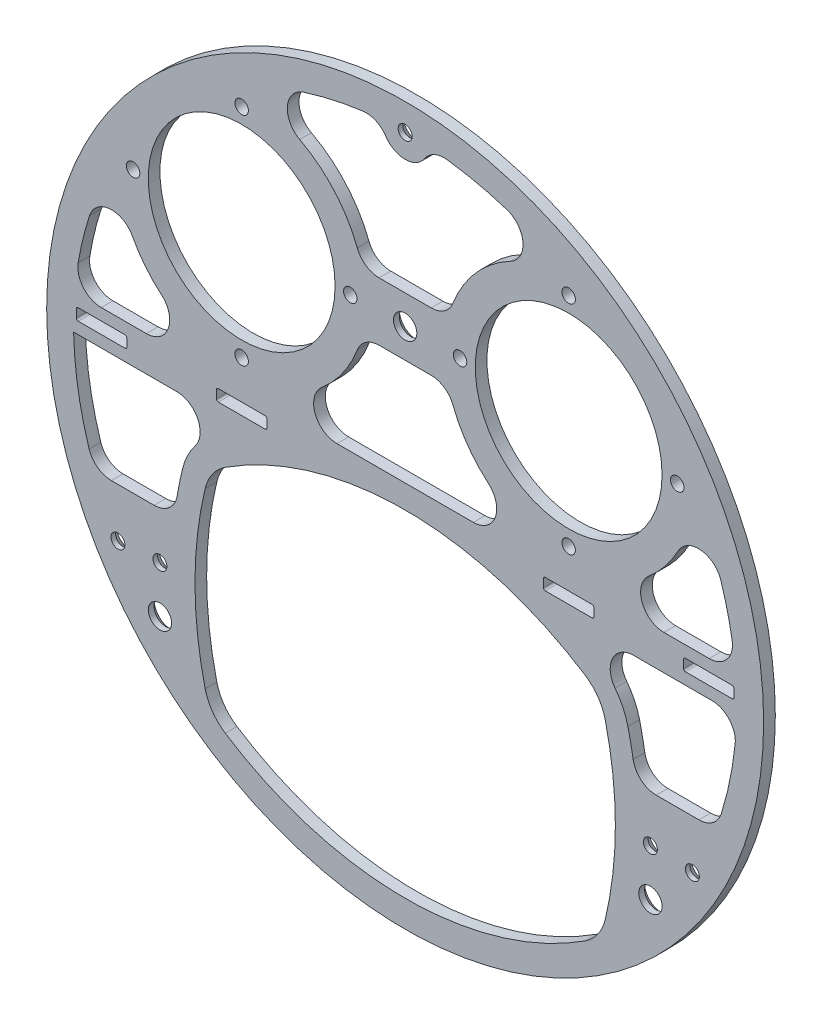
SolidWorks part; units mm, degrees
ref_plane "Front Plane" through (0, 0, 0) normal (0, 0, 1) x (1, 0, 0)
ref_plane "Top Plane" through (0, 0, 0) normal (0, 1, 0) x (1, 0, 0)
ref_plane "Right Plane" through (0, 0, 0) normal (1, 0, 0) x (0, 0, -1)
sketch "Sketch1" plane through (0, 0, 0) normal (0, 0, 1) x (1, 0, 0)
  circle A0 centre (0, 0) radius 97.4725
  circle A1 centre (0, 0) radius 90.17
  dimension "D1" = 194.945
  dimension "D2" = 180.34
extrude "Boss-Extrude1" add sketch "Sketch1" along normal blind 3.175
sketch "Sketch2" plane through (0, 0, 3.175) normal (0, 0, 1) x (1, 0, 0)
  arc A5 (-5.2915, 86.6596) -> (5.2915, 86.6596) centre (0, 90.17) ccw
  circle A6 centre (0, 0) radius 90.17 construction
  arc A8 (-5.2915, 86.6596) -> (-11.3847, 89.4484) centre (-10.5829, 83.1492) ccw
  arc A9 (5.2915, 86.6596) -> (11.3847, 89.4484) centre (10.5829, 83.1492) cw
  arc A10 (11.3847, 89.4484) -> (-11.3847, 89.4484) centre (0, 0) ccw
  dimension "D3" = 6.35
  dimension "D4" = 6.35
extrude "Boss-Extrude2" add sketch "Sketch2" against normal up to surface (3.175 mm away) up to face at (97.4725, 0, 0)
hole_wizard "CSK for #6 Flat Head Machine Screw2" positions "Sketch8" profile "Sketch7" countersink size "#6" standard "ANSI Inch" end condition through all
sketch "Sketch8" plane through (0, 0, 0) normal (0, 0, -1) x (-1, 0, 0)
  point P0 (0, 90.17)
sketch "Sketch7" plane through (0, 90.17, 0) normal (1, 0, 0) x (0, 1, 0)
  line L0 (0, 0) -> (0, 3.175)
  line L1 (0, 3.175) -> (1.8986, 3.175)
  line L2 (1.8986, 3.175) -> (1.8986, 1.892)
  line L3 (1.8986, 1.892) -> (3.5433, 0)
  line L5 (3.5433, 0) -> (0, 0)
  line L6 (-1.8986, 1.892) -> (-3.5433, 0) construction
  line L11 (0, -6.35) -> (0, 107.95) construction
  dimension "Thru Hole Dia." = 3.7973
  dimension "Thru Hole Depth" = 3.175
  dimension "Near C'Sink Dia." = 7.0866
  dimension "Near C'Sink Angle" = 82
pattern_circular "CirPattern2" count 3 over 360 about axis through (0, 0, 0) along (0, 0, 1) of "CSK for #6 Flat Head Machine Screw2", "Boss-Extrude2"
sketch "Sketch9" plane through (0, 0, 0) normal (0, 0, 1) x (1, 0, 0)
  line L0 (44.45, -44.45) -> (-44.45, -44.45) construction
  line L1 (0, 0) -> (0, 1.109) construction
  arc A0 (48.9116, -13.1485) -> (-48.9116, -13.1485) centre (0, -88.9) ccw
  arc A1 (-54.3759, -20.8703) -> (-54.3759, -68.0297) centre (44.45, -44.45) ccw
  arc A2 (-48.9116, -75.7515) -> (48.9116, -75.7515) centre (0, 0) ccw
  arc A3 (-48.9116, -75.7515) -> (-54.3759, -68.0297) centre (-42.0227, -65.0822) cw
  arc A4 (48.9116, -75.7515) -> (54.3759, -68.0297) centre (42.0227, -65.0822) ccw
  arc A5 (54.3759, -68.0297) -> (54.3759, -20.8703) centre (-44.45, -44.45) ccw
  arc A6 (48.9116, -13.1485) -> (54.3759, -20.8703) centre (42.0227, -23.8178) cw
  arc A7 (-48.9116, -13.1485) -> (-54.3759, -20.8703) centre (-42.0227, -23.8178) ccw
  arc A8 (-71.7723, -54.5836) -> (71.7723, -54.5836) centre (0, 0) ccw construction
  arc A9 (-60.5525, -19.3966) -> (-60.5525, -69.5034) centre (44.45, -44.45) ccw
  arc A10 (-52.3561, -81.0861) -> (-60.5525, -69.5034) centre (-42.0227, -65.0822) cw
  arc A11 (-52.3561, -81.0861) -> (52.3561, -81.0861) centre (0, 0) ccw
  arc A12 (52.3561, -81.0861) -> (60.5525, -69.5034) centre (42.0227, -65.0822) ccw
  arc A13 (60.5525, -69.5034) -> (60.5525, -19.3966) centre (-44.45, -44.45) ccw
  arc A14 (52.3561, -7.8139) -> (60.5525, -19.3966) centre (42.0227, -23.8178) cw
  arc A15 (52.3561, -7.8139) -> (-52.3561, -7.8139) centre (0, -88.9) ccw
  arc A16 (-52.3561, -7.8139) -> (-60.5525, -19.3966) centre (-42.0227, -23.8178) ccw
  dimension "D1" = 12.7
  dimension "D4" = 101.6
  dimension "D2" = 44.45
  dimension "D3" = 88.9
  dimension "D5" = 6.35
extrude "Boss-Extrude3" add sketch "Sketch9" along normal up to surface (3.175 mm away) up to face at (-79.9882, -45.085, 3.175)
fillet "Fillet1" radius 3.175 2 edges at (61.3011, -66.1271, 1.5875) (-61.3011, -66.1271, 1.5875)
sketch "Sketch10" plane through (0, 0, 0) normal (0, 0, -1) x (-1, 0, 0)
  line L0 (-84.3953, -31.75) -> (-62.7503, -31.75)
  line L1 (62.7503, -31.75) -> (84.3953, -31.75)
  arc A0 (-11.3847, 89.4484) -> (-83.1569, -34.8648) centre (0, 0) ccw construction
  arc A1 (-60.5525, -19.3966) -> (-62.8448, -56.3258) centre (44.45, -44.45) ccw construction
  arc A2 (62.8448, -56.3258) -> (60.5525, -19.3966) centre (-44.45, -44.45) ccw construction
  arc A3 (83.1569, -34.8648) -> (11.3847, 89.4484) centre (0, 0) ccw construction
  arc A4 (-83.1569, -34.8648) -> (-77.6952, -38.7473) centre (-77.3008, -32.4095) ccw construction
  arc A5 (-72.4037, -47.9124) -> (-77.6952, -38.7473) centre (-78.0895, -45.085) ccw construction
  arc A6 (-72.4037, -47.9124) -> (-71.7723, -54.5836) centre (-66.7179, -50.7397) ccw construction
  arc A7 (-71.7723, -54.5836) -> (-68.4093, -58.7435) centre (0, 0) ccw construction
  arc A8 (-68.4093, -58.7435) -> (-62.8448, -56.3258) centre (-66.0005, -56.6751) ccw construction
  arc A9 (62.8448, -56.3258) -> (68.4093, -58.7435) centre (66.0005, -56.6751) ccw construction
  arc A10 (68.4093, -58.7435) -> (71.7723, -54.5836) centre (0, 0) ccw construction
  arc A11 (71.7723, -54.5836) -> (72.4037, -47.9124) centre (66.7179, -50.7397) ccw construction
  arc A12 (77.6952, -38.7473) -> (72.4037, -47.9124) centre (78.0895, -45.085) ccw construction
  arc A13 (77.6952, -38.7473) -> (83.1569, -34.8648) centre (77.3008, -32.4095) ccw construction
  arc A14 (-84.3953, -31.75) -> (-83.1569, -34.8648) centre (0, 0) ccw
  arc A15 (-83.1569, -34.8648) -> (-77.6952, -38.7473) centre (-77.3008, -32.4095) ccw
  arc A16 (-72.4037, -47.9124) -> (-77.6952, -38.7473) centre (-78.0895, -45.085) ccw
  arc A17 (-72.4037, -47.9124) -> (-71.7723, -54.5836) centre (-66.7179, -50.7397) ccw
  arc A18 (-71.7723, -54.5836) -> (-68.4093, -58.7435) centre (0, 0) ccw
  arc A19 (-62.7503, -31.75) -> (-62.8448, -56.3258) centre (44.45, -44.45) ccw
  arc A20 (-68.4093, -58.7435) -> (-62.8448, -56.3258) centre (-66.0005, -56.6751) ccw
  arc A21 (62.8448, -56.3258) -> (62.7503, -31.75) centre (-44.45, -44.45) ccw
  arc A22 (62.8448, -56.3258) -> (68.4093, -58.7435) centre (66.0005, -56.6751) ccw
  arc A23 (68.4093, -58.7435) -> (71.7723, -54.5836) centre (0, 0) ccw
  arc A24 (71.7723, -54.5836) -> (72.4037, -47.9124) centre (66.7179, -50.7397) ccw
  arc A25 (77.6952, -38.7473) -> (72.4037, -47.9124) centre (78.0895, -45.085) ccw
  arc A26 (77.6952, -38.7473) -> (83.1569, -34.8648) centre (77.3008, -32.4095) ccw
  arc A27 (83.1569, -34.8648) -> (84.3953, -31.75) centre (0, 0) ccw
  dimension "D1" = 31.75
extrude "Boss-Extrude4" add sketch "Sketch10" against normal up to surface (3.175 mm away) up to face at (0, -44.45, 3.175)
sketch "Sketch11" plane through (0, 0, 0) normal (0, 0, -1) x (-1, 0, 0)
  line L0 (0, 0.3556) -> (0, -49999.6444) construction
  circle A0 centre (-66.675, -57.15) radius 3.175
  circle A1 centre (66.675, -57.15) radius 3.175
  arc A2 (48.9116, -13.1485) -> (-48.9116, -13.1485) centre (0, -88.9) ccw construction
  arc A4 (-54.3759, -20.8703) -> (-54.3759, -68.0297) centre (44.45, -44.45) ccw construction
  point P9 (0, 1.27)
  point P19 (-57.15, -44.45)
  dimension "D1" = 6.35
  dimension "D2" = 12.7
  dimension "D3" = 9.525
extrude "Cut-Extrude1" cut sketch "Sketch11" against normal through all
chamfer "Chamfer1" distance 1.5875 angle 45 2 edges at (-69.85, -57.15, 0) (63.5, -57.15, 0)
hole_wizard "CSK for #6 Flat Head Machine Screw1" positions "Sketch13" profile "Sketch12" countersink size "#6" standard "ANSI Inch" end condition through all
sketch "Sketch13" plane through (0, 0, 0) normal (0, 0, -1) x (-1, 0, 0)
  line L0 (-66.675, -57.15) -> (-66.675, -44.45) construction
  line L2 (66.675, -44.45) -> (66.675, -57.15) construction
  arc A1 (-54.3759, -20.8703) -> (-54.3759, -68.0297) centre (44.45, -44.45) ccw construction
  point P0 (66.675, -44.45)
  point P2 (-66.675, -44.45)
  point P23 (-57.15, -44.45)
sketch "Sketch12" plane through (-66.675, -44.45, 0) normal (1, 0, 0) x (0, 1, 0)
  line L0 (0, 0) -> (0, 3.175)
  line L1 (0, 3.175) -> (1.8986, 3.175)
  line L2 (1.8986, 3.175) -> (1.8986, 1.892)
  line L3 (1.8986, 1.892) -> (3.5433, 0)
  line L5 (3.5433, 0) -> (0, 0)
  line L6 (-1.8986, 1.892) -> (-3.5433, 0) construction
  line L11 (0, -6.35) -> (0, 107.95) construction
  dimension "Thru Hole Dia." = 3.7973
  dimension "Thru Hole Depth" = 3.175
  dimension "Near C'Sink Dia." = 7.0866
  dimension "Near C'Sink Angle" = 82
sketch "Sketch14" plane through (0, 0, 0) normal (0, 0, -1) x (-1, 0, 0)
  line L0 (-90.1499, -1.905) -> (-23.7171, -1.905)
  line L1 (-89.8475, 7.62) -> (89.8475, 7.62)
  line L2 (0, 5.3801) -> (0, 50005.3801) construction
  line L3 (-89.408, 4.445) -> (-75.692, 4.445)
  line L4 (-89.408, 4.445) -> (-89.408, 1.27)
  line L5 (-89.408, 1.27) -> (-75.692, 1.27)
  line L6 (-75.692, 4.445) -> (-75.692, 1.27)
  line L7 (89.408, 1.27) -> (75.692, 1.27)
  line L8 (89.408, 1.27) -> (89.408, 4.445)
  line L9 (89.408, 4.445) -> (75.692, 4.445)
  line L10 (75.692, 1.27) -> (75.692, 4.445)
  line L11 (23.7171, -1.905) -> (90.1499, -1.905)
  line L13 (-51.308, 4.445) -> (-37.592, 4.445)
  line L14 (-51.308, 4.445) -> (-51.308, 1.27)
  line L15 (-51.308, 1.27) -> (-37.592, 1.27)
  line L16 (-37.592, 4.445) -> (-37.592, 1.27)
  line L17 (51.308, 4.445) -> (37.592, 4.445)
  line L18 (51.308, 4.445) -> (51.308, 1.27)
  line L19 (51.308, 1.27) -> (37.592, 1.27)
  line L20 (37.592, 4.445) -> (37.592, 1.27)
  arc A0 (-11.3847, 89.4484) -> (-84.3953, -31.75) centre (0, 0) ccw construction
  arc A1 (84.3953, -31.75) -> (11.3847, 89.4484) centre (0, 0) ccw construction
  arc A2 (-89.8475, 7.62) -> (-90.1499, -1.905) centre (0, 0) ccw
  arc A3 (90.1499, -1.905) -> (89.8475, 7.62) centre (0, 0) ccw
  arc A4 (48.9116, -13.1485) -> (-48.9116, -13.1485) centre (0, -88.9) ccw construction
  arc A5 (23.7171, -1.905) -> (-23.7171, -1.905) centre (0, -88.9) ccw
  point P33 (-82.55, 4.445)
  point P34 (82.55, 4.445)
  point P35 (-82.55, 1.27)
  point P36 (-44.45, 1.27)
  point P37 (44.45, 1.27)
  point P38 (82.55, 1.27)
  dimension "D1" = 9.525
  dimension "D2" = 1.905
  dimension "D3" = 3.175
  dimension "D4" = 3.175
  dimension "D5" = 13.716
  dimension "D6" = 165.1
  dimension "D7" = 38.1
  dimension "D8" = 38.1
extrude "Boss-Extrude5" add sketch "Sketch14" against normal up to surface (3.175 mm away) up to face at (-68.5737, -44.45, 3.175)
sketch "Sketch16" plane through (0, 0, 3.175) normal (0, 0, 1) x (1, 0, 0)
  line L0 (0, 0) -> (0, 50000) construction
  line L3 (-48.5775, 11.0491) -> (-48.5775, 7.62)
  line L4 (-11.7444, 36.5125) -> (11.7444, 36.5125)
  line L5 (-11.7444, 52.3875) -> (11.7444, 52.3875)
  line L6 (-19.05, 44.45) -> (19.05, 44.45) construction
  line L7 (-89.8475, 7.62) -> (89.8475, 7.62) construction
  line L8 (-40.3225, 11.0491) -> (-40.3225, 7.62)
  line L9 (-48.5775, 7.62) -> (-40.3225, 7.62)
  line L10 (40.3225, 11.0491) -> (40.3225, 7.62)
  line L11 (40.3225, 7.62) -> (48.5775, 7.62)
  line L12 (48.5775, 7.62) -> (48.5775, 11.0491)
  circle A0 centre (-44.45, 44.45) radius 25.4
  circle A1 centre (44.45, 44.45) radius 25.4
  arc A2 (-78.0993, 45.068) -> (-48.5775, 11.0491) centre (-44.45, 44.45) ccw
  arc A3 (48.5775, 11.0491) -> (78.0993, 45.068) centre (44.45, 44.45) ccw
  arc A4 (-11.3847, 89.4484) -> (-89.8475, 7.62) centre (0, 0) ccw construction
  arc A5 (89.8475, 7.62) -> (11.3847, 89.4484) centre (0, 0) ccw construction
  arc A6 (-45.068, 78.0993) -> (-78.0993, 45.068) centre (0, 0) ccw
  arc A7 (78.0993, 45.068) -> (45.068, 78.0993) centre (0, 0) ccw
  arc A8 (-40.3225, 11.0491) -> (-11.7444, 36.5125) centre (-44.45, 44.45) ccw
  circle A9 centre (-44.45, 44.45) radius 33.655 construction
  arc A10 (45.068, 78.0993) -> (11.7444, 52.3875) centre (44.45, 44.45) ccw
  circle A11 centre (44.45, 44.45) radius 33.655 construction
  arc A12 (-11.7444, 52.3875) -> (-45.068, 78.0993) centre (-44.45, 44.45) ccw
  arc A13 (11.7444, 36.5125) -> (40.3225, 11.0491) centre (44.45, 44.45) ccw
  point P14 (-44.45, 7.62)
  point P19 (-12.7, 44.45)
  point P23 (77.8489, 54.6611)
  point P37 (44.45, 7.62)
  dimension "D2" = 50.8
  dimension "D4" = 8.255
  dimension "D1" = 88.9
  dimension "D3" = 44.45
  dimension "D5" = 15.875
  dimension "D6" = 8.255
extrude "Boss-Extrude6" add sketch "Sketch16" against normal up to surface (3.175 mm away) up to face at (0, -44.45, 0)
fillet "Fillet2" radius 6.35 21 edges at (-84.3953, -31.75, 1.5875) (-62.7503, -31.75, 1.5875) (84.3953, -31.75, 1.5875) (62.7503, -31.75, 1.5875) (90.1499, -1.905, 1.5875) (89.8475, 7.62, 1.5875) (41.8089, -1.905, 1.5875) (-89.8475, 7.62, 1.5875) (78.0993, 45.068, 1.5875) (-78.0993, 45.068, 1.5875) (45.068, 78.0993, 1.5875) (-45.068, 78.0993, 1.5875) (-11.7444, 52.3875, 1.5875) (11.7444, 52.3875, 1.5875) (-11.7444, 36.5125, 1.5875) (11.7444, 36.5125, 1.5875) (48.5775, 11.0491, 1.5875) (40.3225, 11.0491, 1.5875) (-40.3225, 11.0491, 1.5875) (-48.5775, 11.0491, 1.5875) (-41.8089, -1.905, 1.5875)
fillet "Fillet5" radius 6.35 4 edges at (48.5775, 7.62, 1.5875) (40.3225, 7.62, 1.5875) (-48.5775, 7.62, 1.5875) (-40.3225, 7.62, 1.5875)
hole_wizard "#6 Clearance Hole1" positions "Sketch18" profile "Sketch17" hole size "#6" standard "ANSI Inch"
sketch "Sketch18" plane through (0, 0, 3.175) normal (0, 0, 1) x (1, 0, 0)
  line L0 (-10.795, 44.45) -> (-19.05, 44.45)
  circle A0 centre (-44.45, 44.45) radius 33.655
  circle A2 centre (-44.45, 44.45) radius 25.4 construction
  arc A3 (-22.652, 18.8081) -> (-13.0146, 32.4304) centre (-44.45, 44.45) ccw construction
  point P0 (-14.9225, 44.45)
  point P15 (-14.9225, 44.45)
sketch "Sketch17" plane through (-14.9225, 44.45, 3.175) normal (1, 0, 0) x (0, -1, 0)
  line L0 (0, 0) -> (0, 7.4489)
  line L1 (0, 7.4489) -> (1.8288, 6.35)
  line L2 (1.8288, 6.35) -> (1.8288, 0)
  line L5 (1.8288, 0) -> (0, 0)
  line L10 (0, 7.4489) -> (-1.8288, 6.35) construction
  line L11 (0, -6.35) -> (0, 107.95) construction
  dimension "Hole Dia." = 3.6576
  dimension "Hole Depth" = 6.35
  dimension "Drill Angle" = 118
pattern_circular "CirPattern3" count 4 over 360 about axis through (-44.45, 44.45, -171.3759) along (0, 0, 1) of "#6 Clearance Hole1"
mirror "Mirror1" about plane through (0, 0, 0) normal (1, 0, 0) of "CirPattern3"
sketch "Sketch19" plane through (0, 0, 0) normal (0, 0, -1) x (-1, 0, 0)
  line L0 (0, 52.3875) -> (0, 36.5125) construction
  line L1 (7.0833, 52.3875) -> (-7.0833, 52.3875) construction
  line L2 (-7.0833, 36.5125) -> (7.0833, 36.5125) construction
  circle A0 centre (0, 44.45) radius 3.175
  dimension "D1" = 6.35
extrude "Cut-Extrude2" cut sketch "Sketch19" against normal through all
chamfer "Chamfer2" distance 1.5875 angle 45 1 edges at (-3.175, 44.45, 0)
fillet "Fillet6" radius 0.508 16 edges at (-75.692, 4.445, 1.5875) (-75.692, 1.27, 1.5875) (-89.408, 1.27, 1.5875) (-89.408, 4.445, 1.5875) (-51.308, 4.445, 1.5875) (-51.308, 1.27, 1.5875) (-37.592, 1.27, 1.5875) (-37.592, 4.445, 1.5875) (37.592, 4.445, 1.5875) (37.592, 1.27, 1.5875) (51.308, 1.27, 1.5875) (51.308, 4.445, 1.5875) (75.692, 4.445, 1.5875) (75.692, 1.27, 1.5875) (89.408, 1.27, 1.5875) (89.408, 4.445, 1.5875)
